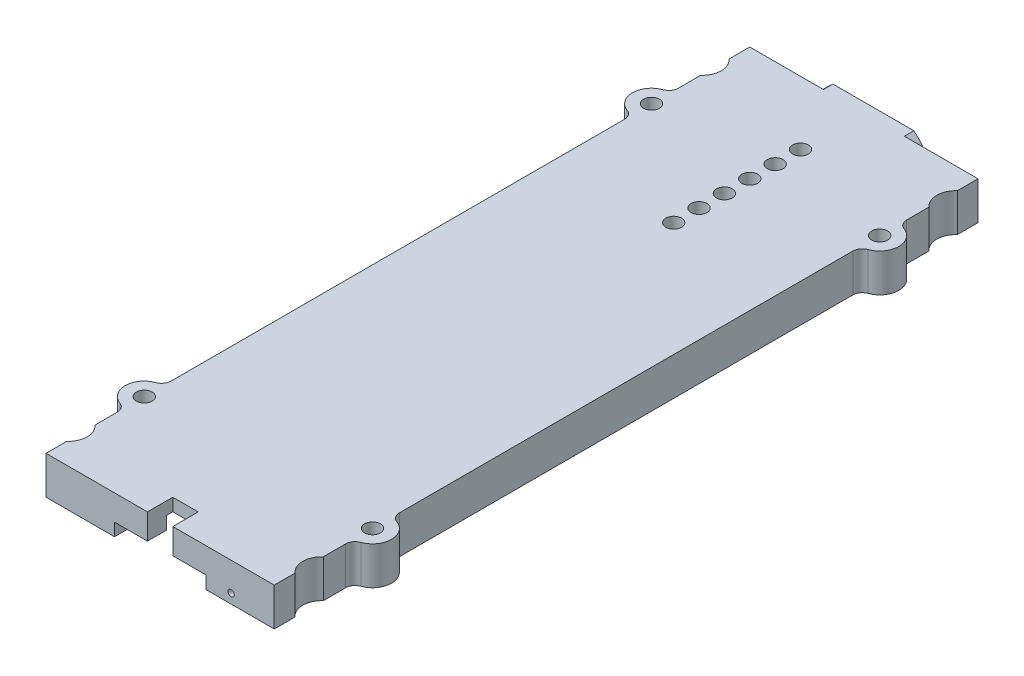
SolidWorks part; units mm, degrees
ref_plane "Спереди" through (0, 0, 0) normal (0, 0, 1) x (1, 0, 0)
ref_plane "Сверху" through (0, 0, 0) normal (0, 1, 0) x (1, 0, 0)
ref_plane "Справа" through (0, 0, 0) normal (1, 0, 0) x (0, 0, -1)
sketch "Эскиз1" plane through (0, 0, 0) normal (0, 1, 0) x (1, 0, 0)
  line L0 (0, 55.5) -> (0, -55.5) construction
  line L1 (-18, 55.5) -> (18, 55.5)
  line L2 (-18, 55.5) -> (-18, -55.5)
  line L3 (-18, -55.5) -> (18, -55.5)
  line L4 (18, 55.5) -> (18, -55.5)
  line L6 (-18, 0) -> (18, 0) construction
  point P8 (0, 0)
  dimension "D1" = 36
  dimension "D2" = 111
extrude "тело" add sketch "Эскиз1" along normal blind 6
sketch "Эскиз2" plane through (0, 6, 0) normal (0, 1, 0) x (1, 0, 0)
  line L0 (-18, 55.5) -> (-18, -55.5) construction
  line L1 (18, -55.5) -> (18, 55.5) construction
  line L2 (0, 55.5) -> (0, -55.5) construction
  line L3 (18, 55.5) -> (-18, 55.5) construction
  line L4 (-18, -55.5) -> (18, -55.5) construction
  line L5 (-18, 37) -> (-18, 43)
  line L6 (18, 43) -> (18, 37)
  line L7 (-18, 40) -> (18, 40) construction
  arc A0 (-18, 43) -> (-18, 37) centre (-18, 40) ccw
  arc A1 (18, 37) -> (18, 43) centre (18, 40) ccw
  dimension "D1" = 3
  dimension "D2" = 40
extrude "наплывы крепления к корпусу" add sketch "Эскиз2" against normal up to surface (6 mm away) up to face at (0, 0, 0)
sketch "Эскиз3" plane through (0, 6, 0) normal (0, 1, 0) x (1, 0, 0)
  circle A0 centre (-18, 40) radius 1.25
  circle A1 centre (18, 40) radius 1.25
  dimension "D1" = 2.5
extrude "крепежные отверстия" cut sketch "Эскиз3" against normal through all
mirror "Зеркальное отражение1" about plane through (0, 0, 0) normal (0, 0, 1) of "наплывы крепления к корпусу", "крепежные отверстия"
sketch "Эскиз4" plane through (0, 0, 0) normal (0, -1, 0) x (1, 0, 0)
  line L0 (15, 52.5) -> (-15, -52.5) construction
  line L1 (-15, 52.5) -> (15, 52.5)
  line L2 (-15, 52.5) -> (-15, -52.5)
  line L3 (-15, -52.5) -> (15, -52.5)
  line L4 (15, 52.5) -> (15, -52.5)
  line L5 (0, 55.5) -> (0, -55.5) construction
  line L6 (-18, 55.5) -> (18, 55.5) construction
  line L7 (18, -55.5) -> (-18, -55.5) construction
  line L8 (-2, -25.5) -> (-2, -45.5)
  line L9 (-18, -37) -> (-18, 37) construction
  line L10 (-18, 0) -> (18, 0) construction
  line L11 (18, 37) -> (18, -37) construction
  line L13 (2, -25.5) -> (2, -45.5)
  arc A0 (2, -25.5) -> (-2, -25.5) centre (0, -25.5) ccw
  arc A1 (-2, -45.5) -> (2, -45.5) centre (0, -45.5) ccw
  point P13 (0, 0)
  dimension "D3" = 2
  dimension "D1" = 30
  dimension "D2" = 105
  dimension "D4" = 20
  dimension "D5" = 7
extrude "вырез под плату" cut sketch "Эскиз4" against normal blind 4
sketch "Эскиз5" plane through (0, 0, 0) normal (0, -1, 0) x (1, 0, 0)
  line L0 (-18, 55.5) -> (18, 55.5) construction
  line L1 (-7.2, 0) -> (7.2, 0)
  line L2 (-7.2, 0) -> (-7.2, 55.5)
  line L3 (-7.2, 55.5) -> (7.2, 55.5)
  line L4 (7.2, 0) -> (7.2, 55.5)
  point P4 (0, 0)
  dimension "D1" = 14.4
extrude "вырез под rj45" cut sketch "Эскиз5" against normal blind 2
sketch "Эскиз6" plane through (0, 2, 0) normal (0, -1, 0) x (1, 0, 0)
  line L0 (7.2, 55.5) -> (-7.2, 55.5) construction
  line L1 (-2, 55.5) -> (2, 55.5)
  line L2 (-2, 55.5) -> (-2, 51.5)
  line L3 (-2, 51.5) -> (2, 51.5)
  line L4 (2, 55.5) -> (2, 51.5)
  point P4 (0, 55.5)
  point P7 (0, 55.5)
  dimension "D1" = 4
extrude "вырез под ушко rj45" cut sketch "Эскиз6" against normal through all
sketch "Эскиз7" plane through (0, 0, 0) normal (0, -1, 0) x (1, 0, 0)
  line L0 (-15, -52.5) -> (15, -52.5) construction
  line L1 (-5, -52.5) -> (5, -52.5)
  line L2 (-5, -52.5) -> (-5, -55.5)
  line L3 (-5, -55.5) -> (5, -55.5)
  line L4 (5, -52.5) -> (5, -55.5)
  line L5 (18, -55.5) -> (-18, -55.5) construction
  point P4 (0, -52.5)
  point P7 (0, -52.5)
  dimension "D1" = 10
extrude "вырез под sma" cut sketch "Эскиз7" against normal blind 3
sketch "Эскиз8" plane through (0, 0, -55.5) normal (0, 0, -1) x (-1, 0, 0)
  line L0 (0, 6) -> (0, 0) construction
  line L1 (-18, 6) -> (18, 6) construction
  line L2 (-18, 0) -> (-5, 0) construction
  line L3 (-6.3804, 6) -> (6.3804, 6)
  line L4 (-9.8544, 0) -> (-2.4718, 0)
  line L5 (2.4718, 0) -> (9.8544, 0)
  line L6 (5, 0) -> (18, 0) construction
  arc A0 (-6.3804, 6) -> (-9.8544, 0) centre (0, -1.7) ccw
  arc A1 (2.4718, 0) -> (-2.4718, 0) centre (0, -1.7) ccw
  arc A2 (9.8544, 0) -> (6.3804, 6) centre (0, -1.7) ccw
  dimension "D1" = 1.7
  dimension "D2" = 6
  dimension "D3" = 20
extrude "наплыв под sma" add sketch "Эскиз8" along normal blind 1.5
sketch "Эскиз9" plane through (0, 0, 0) normal (0, -1, 0) x (1, 0, 0)
  line L0 (7.2, 52.5) -> (15, 52.5)
  line L1 (7.2, 52.5) -> (7.2, 54.5)
  line L2 (15, 52.5) -> (15, 54.5)
  line L3 (7.2, 54.5) -> (15, 54.5)
  dimension "D1" = 2
extrude "вырез под reset" cut sketch "Эскиз9" against normal up to surface (2 mm away) up to face at (4.6, 2, 54)
sketch "Эскиз10" plane through (0, 6, 0) normal (0, 1, 0) x (1, 0, 0)
  line L0 (0, 57) -> (0, -51.5) construction
  line L1 (-6.3804, 57) -> (6.3804, 57) construction
  line L2 (-2, -51.5) -> (2, -51.5) construction
  line L3 (-20, 50) -> (20, 50) construction
  circle A0 centre (-20, 50) radius 3
  circle A1 centre (20, 50) radius 3
  dimension "D1" = 6
  dimension "D2" = 40
  dimension "D3" = 50
extrude "вырез под шляпки болтов" cut sketch "Эскиз10" against normal through all
mirror "Зеркальное отражение2" about plane through (0, 0, 0) normal (0, 0, 1) of "вырез под шляпки болтов"
sketch "Эскиз11" plane through (0, 0, 0) normal (0, -1, 0) x (1, 0, 0)
  circle A0 centre (0, -45.5) radius 1.25
  dimension "D1" = 2.5
extrude "отверстие под светодиод" cut sketch "Эскиз11" against normal through all
pattern_linear "Линейный массив1" count 6 spacing 4 along (0, 0, 1) of "отверстие под светодиод"
sketch "Эскиз12" plane through (0, 0, 55.5) normal (0, 0, 1) x (1, 0, 0)
  line L0 (7.2, 2) -> (18, 2) construction
  line L1 (18, 6) -> (18, 0) construction
  line L2 (7.2, 2) -> (7.2, 0) construction
  circle A0 centre (11.2, 1.5) radius 0.5
  dimension "D1" = 1
  dimension "D2" = 4
extrude "отверстие под reset" cut sketch "Эскиз12" against normal up to surface (1 mm away) up to face at (11.1, 1, 54.5)
fillet "Скругление1" radius 1.5 8 edges at (-18, 3, 43) (-18, 3, 37) (-18, 3, -37) (-18, 3, -43) (18, 3, -43) (18, 3, -37) (18, 3, 37) (18, 3, 43)
